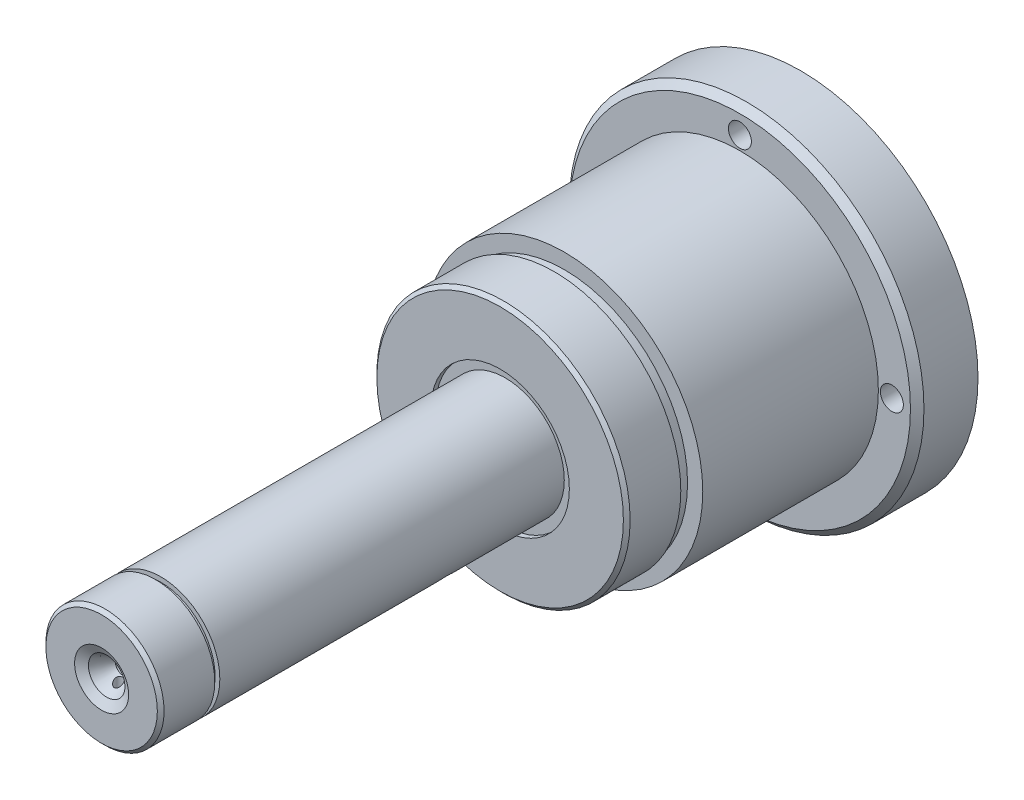
SolidWorks part; units mm, degrees
ref_plane "前视基准面" through (0, 0, 0) normal (0, 0, 1) x (1, 0, 0)
ref_plane "上视基准面" through (0, 0, 0) normal (0, 1, 0) x (1, 0, 0)
ref_plane "右视基准面" through (0, 0, 0) normal (1, 0, 0) x (0, 0, -1)
other "Configuration Table"
sketch "草图1" plane through (0, 0, 0) normal (0, 0, 1) x (1, 0, 0)
  circle A0 centre (0, 0) radius 52.5
  dimension "D1" = 105
extrude "凸台-拉伸1" add sketch "草图1" along normal blind 18
sketch "草图2" plane through (0, 0, 18) normal (0, 0, 1) x (1, 0, 0)
  circle A0 centre (0, 0) radius 41
  dimension "D1" = 82
extrude "凸台-拉伸2" add sketch "草图2" along normal blind 52
chamfer "倒角1" distance 2 angle 45 1 edges at (52.5, 0, 18)
sketch "草图3" plane through (0, 0, 70) normal (0, 0, 1) x (1, 0, 0)
  circle A0 centre (0, 0) radius 36.5
  dimension "D1" = 73
extrude "凸台-拉伸3" add sketch "草图3" along normal blind 3
sketch "草图4" plane through (0, 0, 73) normal (0, 0, 1) x (1, 0, 0)
  circle A0 centre (0, 0) radius 37.5
  dimension "D1" = 75
extrude "凸台-拉伸4" add sketch "草图4" along normal blind 16
sketch "草图5" plane through (0, 0, 0) normal (0, 0, -1) x (-1, 0, 0)
  circle A0 centre (0, 0) radius 32.5
  dimension "D1" = 65
extrude "切除-拉伸1" cut sketch "草图5" against normal blind 79 contours A0
sketch "草图6" plane through (0, 0, 79) normal (0, 0, -1) x (-1, 0, 0)
  circle A0 centre (0, 0) radius 34
  dimension "D1" = 68
extrude "切除-拉伸2" cut sketch "草图6" against normal blind 3 contours A0
sketch "草图7" plane through (0, 0, 89) normal (0, 0, 1) x (1, 0, 0)
  circle A0 centre (0, 0) radius 17.5
  dimension "D1" = 35
extrude "凸台-拉伸5" add sketch "草图7" along normal blind 118
sketch "草图16" plane through (0, 0, 0) normal (1, 0, 0) x (0, 0, -1)
  line L0 (-82, 0) -> (-122.6818, 0) construction
  line L2 (-82, 8.6547) -> (-84, 7.5)
  line L3 (-84, 7.5) -> (-102, 7.5)
  line L4 (-102, 7.5) -> (-104.103, 4)
  line L5 (-104.103, 4) -> (-174, 4)
  line L6 (-174, 4) -> (-176.4034, 0)
  line L7 (-82, -34) -> (-82, 34) construction
  line L8 (-82, 8.6547) -> (-82, 0)
  line L9 (-176.4034, 0) -> (-82, 0)
  dimension "D1" = 20
  dimension "D2" = 59
  dimension "D3" = 59
  dimension "D4" = 8
  dimension "D5" = 15
  dimension "D6" = 92
  dimension "D7" = 2
  dimension "D8" = 30
revolve "切除-旋转1" cut sketch "草图16" angle 360 about L0
sketch "草图17" plane through (0, 0, 0) normal (1, 0, 0) x (0, 0, -1)
  line L0 (-70, 0) -> (-167.5, 0) construction
  line L1 (-207, 8) -> (-207, 0)
  line L2 (-167.5, 0) -> (-167.5, -17.5) construction
  line L3 (-207, 8) -> (-205.5, 5.4019)
  line L4 (-207, 17.5) -> (-207, -17.5) construction
  line L5 (-205.5, 5.4019) -> (-200.4737, 2.5)
  line L6 (-200.4737, 2.5) -> (-184, 2.5)
  line L7 (-184, 2.5) -> (-182.4978, 0)
  line L8 (-70, 41) -> (-70, -41) construction
  line L9 (-182.4978, 0) -> (-207, 0)
  line L10 (-202, 0) -> (-202, -17.5) construction
  line L11 (-204.5, -17.5) -> (-204.5, -9.5)
  line L12 (-204.5, -9.5) -> (-203.5, -8.8991)
  line L13 (-203.5, -8.8991) -> (-202, -8.8991)
  line L14 (-204.5, -17.5) -> (-202, -17.5)
  line L15 (-202, -8.8991) -> (-202, -17.5)
  dimension "D1" = 60
  dimension "D2" = 16
  dimension "D3" = 1.5
  dimension "D4" = 30
  dimension "D5" = 5
  dimension "D6" = 59
  dimension "D7" = 23
  dimension "D8" = 97.5
  dimension "D9" = 5
  dimension "D10" = 5
  dimension "D11" = 3
  dimension "D12" = 59
  dimension "D13" = 8
  dimension "D14" = 17.5
revolve "切除-旋转2" cut sketch "草图17" angle 360 about L0
hole_wizard "Ø8.0mm 暗销孔1" positions "3D草图1" profile "草图18" hole size "Ø8.0" standard "GB" end condition up to next
sketch3d "3D草图1"
  point P0 (0, -17.5, 167.5)
sketch "草图18" plane through (0, -17.5, 167.5) normal (1, 0, 0) x (0, 0, -1)
  line L0 (0, 0) -> (0, 13.5)
  line L1 (0, 13.5) -> (4, 13.5)
  line L2 (4, 13.5) -> (4, 0)
  line L5 (4, 0) -> (0, 0)
  line L11 (0, -6.35) -> (0, 107.95) construction
  dimension "通孔孔直径" = 8
  dimension "通孔孔深度" = 13.5
revolve "切除-旋转4" cut sketch "草图17<3>" angle 360 about L15
sketch "草图17<3>" plane through (0, 0, 0) normal (1, 0, 0) x (0, 0, -1) same geometry as "草图17"
hole_wizard "M3 螺纹孔2" positions "3D草图7" profile "草图24" tap size "M3" standard "GB" end condition up to next
sketch3d "3D草图7"
  point P0 (0, -8.8991, 202)
  point P3 (0, -8.8991, 202)
sketch "草图24" plane through (0, -8.8991, 202) normal (1, 0, 0) x (0, 0, -1)
  line L0 (0, 0) -> (0, 8.8991)
  line L1 (0, 8.8991) -> (1.25, 8.8991)
  line L2 (1.25, 8.8991) -> (1.25, 0)
  line L5 (1.25, 0) -> (0, 0)
  line L11 (0, -6.35) -> (0, 107.95) construction
  dimension "通孔螺纹孔钻头直径" = 2.5
  dimension "通孔螺纹孔钻头深度" = 8.8991
cosmetic thread "孔螺纹线3" parameters "D2"=3
sketch "草图26" plane through (0, 0, 0) normal (0, 0, 1) x (1, 0, 0)
  circle A0 centre (0, 0) radius 16.1
  circle A1 centre (0, 0) radius 17.5 construction
  circle A2 centre (0, 0) radius 17.5
  dimension "D1" = 32.2
extrude "切除-拉伸6" cut sketch "草图26" along normal blind 1.5 from offset 189.5
sketch "草图28" plane through (0, 0, 0) normal (0, 0, 1) x (1, 0, 0)
  circle A0 centre (0, 0) radius 17.5 construction
  circle A1 centre (0, 0) radius 17.5
  circle A2 centre (0, 0) radius 20.5
  dimension "D1" = 3
extrude "切除-拉伸7" cut sketch "草图28" against normal blind 1.5 from offset 89
sketch "草图30" plane through (0, 0, 0) normal (0, 0, -1) x (-1, 0, 0)
  line L0 (0, 0) -> (0, 45) construction
  point P1 (0, 45)
  point P7 (0, 45)
hole_wizard "M8 螺纹孔1" positions "草图30" profile "草图31" tap size "M8" standard "GB" end condition up to next
sketch "草图31" plane through (0, 45, 0) normal (1, 0, 0) x (0, 1, 0)
  line L0 (0, 0) -> (0, 18)
  line L1 (0, 18) -> (3.4, 18)
  line L2 (3.4, 18) -> (3.4, 0)
  line L5 (3.4, 0) -> (0, 0)
  line L11 (0, -6.35) -> (0, 107.95) construction
  dimension "通孔螺纹孔钻头直径" = 6.8
  dimension "通孔螺纹孔钻头深度" = 18
cosmetic thread "孔螺纹线4" parameters "D2"=8
pattern_circular "阵列(圆周)1" count 4 over 360 about axis through (0, 0, 0) along (0, 0, 1) of "M8 螺纹孔1"
ref_plane "基准面1" through (0, 0, 118) normal (0, 0, 1) x (1, 0, 0)
ref_plane "基准面2" through (0, 0, 144) normal (0, 0, 1) x (1, 0, 0)
sketch "草图32" plane through (0, 0, 118) normal (0, 0, 1) x (1, 0, 0)
  line L0 (0, 0) -> (0, -11.4192) construction
  line L1 (0, 0) -> (-11.2488, -13.4058)
  line L2 (0, 0) -> (11.2488, -13.4058)
  circle A0 centre (0, 0) radius 17.5 construction
  circle A1 centre (0, 0) radius 17.5
  dimension "D1" = 80
sketch "草图33" plane through (0, 0, 144) normal (0, 0, 1) x (1, 0, 0)
  line L0 (0, 0) -> (11.2488, -13.4058) construction
  line L1 (0, 0) -> (-11.2488, -13.4058) construction
  line L2 (0, 0) -> (11.2488, -13.4058)
  line L3 (0, 0) -> (-11.2488, -13.4058)
hole_wizard "Ø6.0mm 暗销孔1" positions "3D草图8" profile "草图35" hole size "Ø6.0" standard "GB"
sketch3d "3D草图8"
  point P0 (11.2488, -13.4058, 118)
  point P2 (-11.2488, -13.4058, 144)
sketch "草图35" plane through (11.2488, -13.4058, 118) normal (0, 0, 1) x (0.766, 0.6428, 0)
  line L0 (0, 0) -> (0, 11.8026)
  line L1 (0, 11.8026) -> (3, 10)
  line L2 (3, 10) -> (3, 0)
  line L5 (3, 0) -> (0, 0)
  line L10 (0, 11.8026) -> (-3, 10) construction
  line L11 (0, -6.35) -> (0, 107.95) construction
  dimension "孔直径" = 6
  dimension "孔深度" = 10
  dimension "导头角度" = 118
hole_wizard "M6 螺纹孔1" positions "3D草图9" profile "草图36" tap size "M6" standard "GB"
sketch3d "3D草图9"
  point P0 (11.2488, -13.4058, 144)
  point P2 (-11.2488, -13.4058, 118)
sketch "草图36" plane through (11.2488, -13.4058, 144) normal (0, 0, 1) x (0.766, 0.6428, 0)
  line L0 (0, 0) -> (0, 11.5022)
  line L1 (0, 11.5022) -> (2.5, 10)
  line L2 (2.5, 10) -> (2.5, 0)
  line L5 (2.5, 0) -> (0, 0)
  line L10 (0, 11.5022) -> (-2.5, 10) construction
  line L11 (0, -6.35) -> (0, 107.95) construction
  dimension "螺纹孔钻头直径" = 5
  dimension "螺纹孔钻头深度" = 10
  dimension "导头角度" = 118
cosmetic thread "孔螺纹线5" parameters "D1"=8, "D2"=6
cosmetic thread "孔螺纹线6" parameters "D1"=8, "D2"=6
chamfer "倒角2" distance 1 angle 45 3 edges at (-32.5, 0, 0) (17.5, 0, 207) (37.5, 0, 89)
